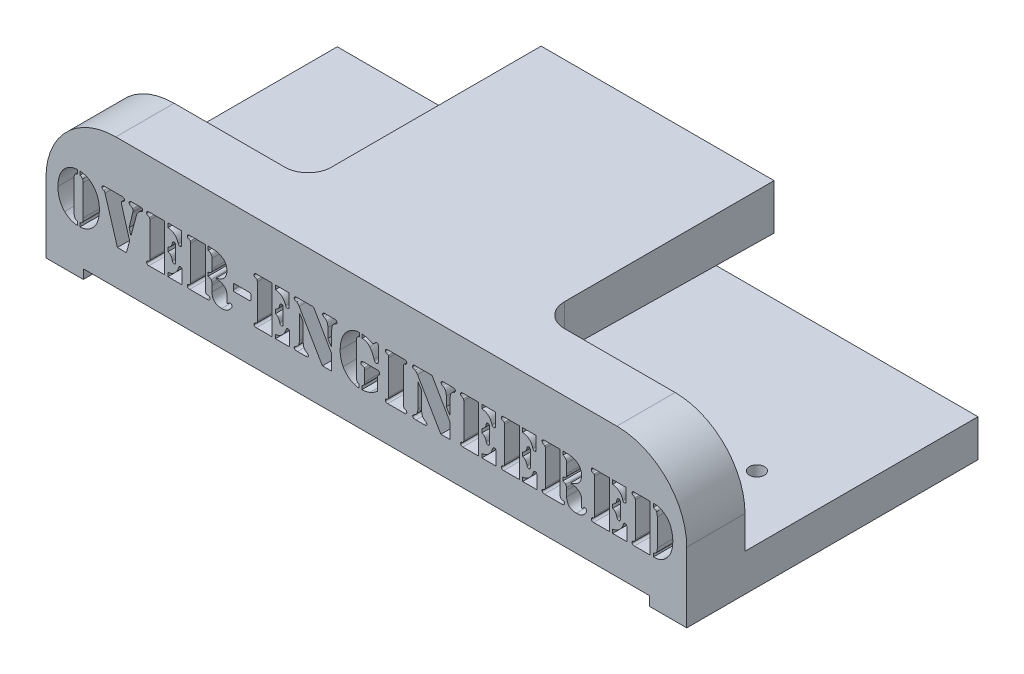
SolidWorks part; units mm, degrees
ref_plane "Front Plane" through (0, 0, 0) normal (0, 0, 1) x (1, 0, 0)
ref_plane "Top Plane" through (0, 0, 0) normal (0, 1, 0) x (1, 0, 0)
ref_plane "Right Plane" through (0, 0, 0) normal (1, 0, 0) x (0, 0, -1)
sketch "Sketch1" plane through (0, 0, 0) normal (0, 1, 0) x (1, 0, 0)
  line L1 (-34.925, -15.875) -> (34.925, -15.875)
  line L2 (-34.925, -15.875) -> (-34.925, 15.875)
  line L3 (-34.925, 15.875) -> (34.925, 15.875)
  line L4 (34.925, -15.875) -> (34.925, 15.875)
  line L5 (-34.925, -15.875) -> (34.925, 15.875) construction
  line L6 (-34.925, 15.875) -> (34.925, -15.875) construction
  point P0 (0, 0)
  dimension "D1" = 31.75
  dimension "D2" = 69.85
extrude "Boss-Extrude1" add sketch "Sketch1" along normal blind 15.24
sketch "Sketch2" plane through (-34.925, 0, 0) normal (-1, 0, 0) x (0, 0, 1)
  line L0 (-15.875, 15.24) -> (-15.875, 0) construction
  line L1 (-15.875, 10.414) -> (9.525, 10.414)
  line L2 (-15.875, 10.414) -> (-15.875, 4.064)
  line L3 (-15.875, 4.064) -> (9.525, 4.064)
  line L4 (9.525, 10.414) -> (9.525, 4.064)
  dimension "D1" = 6.35
  dimension "D2" = 25.4
  dimension "D3" = 4.064
extrude "Cut-Extrude1" cut sketch "Sketch2" against normal up to surface (69.85 mm away) up to face at (34.925, 7.62, 0)
sketch "Sketch3" plane through (-34.925, 0, 0) normal (-1, 0, 0) x (0, 0, 1)
  line L0 (9.525, 10.414) -> (-15.875, 10.414) construction
  line L1 (-15.875, 15.24) -> (9.525, 15.24)
  line L2 (-15.875, 15.24) -> (-15.875, 10.414)
  line L3 (-15.875, 10.414) -> (9.525, 10.414)
  line L4 (9.525, 15.24) -> (9.525, 10.414)
  dimension "D1" = 25.4
extrude "Cut-Extrude2" cut sketch "Sketch3" against normal blind 50.8
mirror "Mirror1" about plane through (0, 0, 0) normal (1, 0, 0) of "Cut-Extrude2"
sketch "Sketch5" plane through (0, 0, 0) normal (0, -1, 0) x (1, 0, 0)
  line L0 (-27.9908, 1.2954) -> (27.9908, 1.2954) construction
  line L1 (-34.925, 15.875) -> (34.925, 15.875) construction
  line L3 (-30.861, 15.875) -> (30.861, 15.875)
  line L4 (-30.861, 15.875) -> (-30.861, -1.2446)
  line L5 (-30.861, -1.2446) -> (30.861, -1.2446)
  line L6 (30.861, 15.875) -> (30.861, -1.2446)
  circle A0 centre (-27.9908, 1.2954) radius 0.8192
  circle A1 centre (27.9908, 1.2954) radius 0.8192
  point P0 (-27.9908, 1.2954)
  point P1 (27.9908, 1.2954)
  point P2 (0, 1.2954)
  point P12 (0, -1.2446)
  point P18 (0, -1.2446)
  line M3 (34.925, 15.875) -> (-34.925, 15.875)
  dimension "D5" = 1.6383
  dimension "D6" = 1.6383
  dimension "D1" = 2.54
  dimension "D2" = 55.9816
  dimension "D3" = 17.1196
  dimension "D4" = 61.722
extrude "Cut-Extrude3" cut sketch "Sketch5" against normal blind 1.016 contours L6 L4 L5 A0 A1 M3 | A0 | A1 region at (0, 0, 7.3393) region at (-27.9908, 0, 1.2954) region at (27.9908, 0, 1.2954)
extrude "Cut-Extrude4" cut sketch "Sketch5<3>" against normal through all contours A0 | A1 region at (-27.9908, 0, 1.2954) region at (27.9908, 0, 1.2954)
sketch "Sketch5<3>" plane through (0, 0, 0) normal (0, -1, 0) x (1, 0, 0) same geometry as "Sketch5"
sketch "Sketch7" plane through (0, 0, 9.525) normal (0, 0, -1) x (-1, 0, 0)
  line L0 (-34.925, 15.24) -> (34.925, 15.24) construction
  line L1 (-34.925, 9.144) -> (34.925, 9.144)
  line L2 (-34.925, 9.144) -> (-34.925, 15.24)
  line L3 (-34.925, 15.24) -> (34.925, 15.24)
  line L4 (34.925, 9.144) -> (34.925, 15.24)
  line L5 (-34.925, 9.144) -> (34.925, 15.24) construction
  line L6 (-34.925, 15.24) -> (34.925, 9.144) construction
  line L7 (-34.925, 4.064) -> (34.925, 4.064) construction
  point P0 (0, 12.192)
  dimension "D1" = 5.08
  dimension "D2" = 69.85
extrude "Boss-Extrude2" add sketch "Sketch7" along normal blind 25.4
sketch "Sketch8" plane through (-34.925, 0, 0) normal (-1, 0, 0) x (0, 0, 1)
  line L0 (-15.875, 10.287) -> (9.525, 10.668)
  line L1 (-15.875, 9.144) -> (-15.875, 15.24) construction
  line L3 (-15.875, 9.144) -> (9.525, 9.144) construction
  line L5 (9.525, 9.144) -> (9.525, 4.064) construction
  line L6 (-15.875, 10.287) -> (-15.875, 9.144)
  line L7 (-15.875, 9.144) -> (9.525, 9.144)
  line L8 (9.525, 9.144) -> (9.525, 10.668)
  dimension "D1" = 1.143
  dimension "D2" = 1.524
extrude "Cut-Extrude9" cut sketch "Sketch8" against normal through all both and the other way through all
sketch "Sketch17" plane through (0, 0, -15.875) normal (0, 0, -1) x (-1, 0, 0)
  line L0 (34.925, 15.24) -> (-34.925, 15.24) construction
  line L1 (-12.7, 15.24) -> (12.7, 15.24)
  line L2 (-12.7, 15.24) -> (-12.7, 10.287)
  line L3 (-12.7, 10.287) -> (12.7, 10.287)
  line L4 (12.7, 15.24) -> (12.7, 10.287)
  line L5 (-34.925, 10.287) -> (34.925, 10.287) construction
  line L7 (-12.7, 15.24) -> (-34.925, 15.24)
  line L8 (-12.7, 15.24) -> (-12.7, 10.287)
  line L9 (-12.7, 10.287) -> (-34.925, 10.287)
  line L10 (-34.925, 15.24) -> (-34.925, 10.287)
  line L11 (12.7, 15.24) -> (34.925, 15.24)
  line L12 (12.7, 15.24) -> (12.7, 10.287)
  line L13 (12.7, 10.287) -> (34.925, 10.287)
  line L14 (34.925, 15.24) -> (34.925, 10.287)
  point P13 (0, 15.24)
  line M4 (-34.925, 15.24) -> (-34.925, 10.287)
  line M5 (-34.925, 10.287) -> (34.925, 10.287)
  line M6 (34.925, 10.287) -> (34.925, 15.24)
  line M7 (34.925, 15.24) -> (-34.925, 15.24)
  dimension "D1" = 25.4
extrude "Cut-Extrude13" cut sketch "Sketch17" against normal up to surface (25.4 mm away) contours L2 M7 M4 M5 | L4 M7 M5 M6 region at (23.8125, 12.7635, -15.875) region at (-23.8125, 12.7635, -15.875) up to face at (0, 7.366, 9.525)
fillet "Fillet1" radius 2.54 2 edges at (12.7, 12.954, 9.525) (-12.7, 12.954, 9.525)
fillet "Fillet3" radius 7.62 2 edges at (-34.925, 15.24, 12.7) (34.925, 15.24, 12.7)
sketch "Sketch18" plane through (0, 0, 15.875) normal (0, 0, 1) x (1, 0, 0)
  text T0 "Over-Engineered" font "Stencil" height 5.08
  point P3 (-31.3103, 5.8164)
  point P5 (-33.7632, 5.8164)
  point P6 (0, 0)
  dimension "D1" = 33.7632
  dimension "D2" = 4.8785
extrude "Cut-Extrude14" cut sketch "Sketch18" against normal blind 2.54
